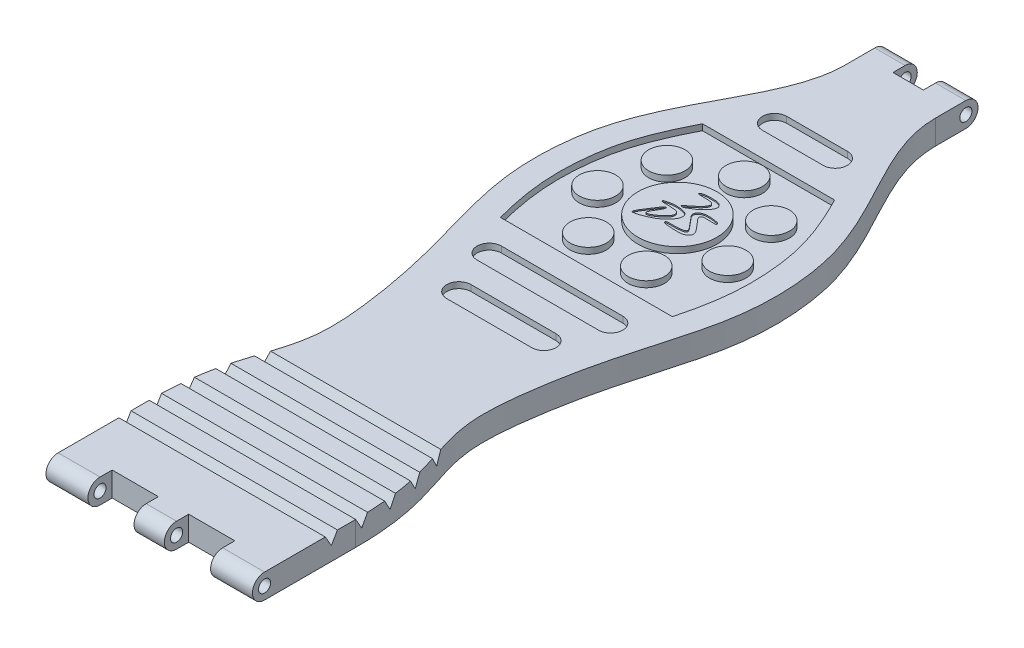
SolidWorks part; units mm, degrees
ref_plane "Front Plane" through (0, 0, 0) normal (0, 0, 1) x (1, 0, 0)
ref_plane "Top Plane" through (0, 0, 0) normal (0, 1, 0) x (1, 0, 0)
ref_plane "Right Plane" through (0, 0, 0) normal (1, 0, 0) x (0, 0, -1)
other "Configuration Table"
sketch "Sketch1" plane through (0, 0, 0) normal (0, 1, 0) x (1, 0, 0)
  line L0 (0, 0) -> (0, 152.4) construction
  line L2 (-21.59, 0) -> (21.59, 0)
  line L3 (-21.59, 0) -> (-21.59, 19.05)
  line L4 (-21.59, 19.05) -> (21.59, 19.05)
  line L5 (21.59, 0) -> (21.59, 19.05)
  line L6 (-21.59, 0) -> (21.59, 19.05) construction
  line L7 (-21.59, 19.05) -> (21.59, 0) construction
  line L8 (-9.525, 152.4) -> (9.525, 152.4)
  line L9 (-9.525, 152.4) -> (-9.525, 158.75)
  line L10 (-9.525, 158.75) -> (9.525, 158.75)
  line L11 (9.525, 152.4) -> (9.525, 158.75)
  line L12 (-9.525, 152.4) -> (9.525, 158.75) construction
  line L13 (-9.525, 158.75) -> (9.525, 152.4) construction
  spline S0 degree 3 poles (-9.525, 152.4) (-9.525, 140.7805) (-22.9495, 127.2801) (-26.9071, 91.7166) (-18.6052, 80.0483) (-14.4166, 41.5339) (-21.59, 36.242) (-21.59, 19.05) knots 0 0 0 0 0.318102 0.39652 0.741104 0.805759 1 1 1 1
  spline S1 degree 3 poles (9.525, 152.4) (9.525, 140.7805) (22.9495, 127.2801) (26.9071, 91.7166) (18.6052, 80.0483) (14.4166, 41.5339) (21.59, 36.242) (21.59, 19.05) knots 0 0 0 0 0.318102 0.39652 0.741104 0.805759 1 1 1 1
  point P7 (0, 9.525)
  point P12 (0, 155.575)
  dimension "D1" = 152.4
  dimension "D2" = 43.18
  dimension "D3" = 19.05
  dimension "D4" = 19.05
  dimension "D5" = 6.35
extrude "Boss-Extrude1" add sketch "Sketch1" against normal blind 5.08 contours S1 L8 S0 L4 | L2 L5 L4 L3 | L8 L11 L10 L9 region at (0, 0, -9.525) region at (0, 0, -84.0947) region at (0, 0, -155.575)
sketch "Sketch2" plane through (-21.59, 0, 0) normal (-1, 0, 0) x (0, 0, 1)
  line L0 (0, -5.08) -> (0, 0) construction
  circle A0 centre (0, -2.54) radius 2.54
extrude "Boss-Extrude2" add sketch "Sketch2" against normal up to surface (43.18 mm away) up to face at (21.59, -2.54, -9.525)
sketch "Sketch3" plane through (-9.525, 0, 0) normal (-1, 0, 0) x (0, 0, 1)
  line L0 (-158.75, -5.08) -> (-158.75, 0) construction
  circle A0 centre (-158.75, -2.54) radius 2.54
extrude "Boss-Extrude3" add sketch "Sketch3" against normal up to surface (19.05 mm away) up to face at (9.525, -2.54, -155.575)
sketch "Sketch4" plane through (-9.525, 0, 0) normal (-1, 0, 0) x (0, 0, 1)
  circle A0 centre (-158.75, -2.54) radius 1.27
  dimension "D1" = 2.54
extrude "Cut-Extrude1" cut sketch "Sketch4" against normal up to surface (19.05 mm away) up to face at (9.525, -2.54, -156.21)
sketch "Sketch5" plane through (-21.59, 0, 0) normal (-1, 0, 0) x (0, 0, 1)
  circle A0 centre (0, -2.54) radius 1.27
  dimension "D1" = 2.54
extrude "Cut-Extrude2" cut sketch "Sketch5" against normal up to surface (43.18 mm away) up to face at (21.59, -2.54, -8.89)
sketch "Sketch6" plane through (0, 0, 0) normal (0, 1, 0) x (1, 0, 0)
  line L0 (9.525, 161.29) -> (-9.525, 161.29) construction
  line L1 (-3.175, 2.54) -> (-12.827, 2.54)
  line L2 (-3.175, 2.54) -> (-3.175, -2.54)
  line L3 (-3.175, -2.54) -> (-12.827, -2.54)
  line L4 (-12.827, 2.54) -> (-12.827, -2.54)
  line L5 (-3.175, 2.54) -> (-12.827, -2.54) construction
  line L6 (-3.175, -2.54) -> (-12.827, 2.54) construction
  line L7 (-21.59, -2.54) -> (21.59, -2.54) construction
  line L8 (-3.175, 2.54) -> (3.175, 2.54) construction
  line L9 (3.175, 2.54) -> (12.827, 2.54)
  line L10 (3.175, 2.54) -> (3.175, -2.54)
  line L11 (3.175, -2.54) -> (12.827, -2.54)
  line L12 (12.827, 2.54) -> (12.827, -2.54)
  line L13 (3.175, 2.54) -> (12.827, -2.54) construction
  line L14 (3.175, -2.54) -> (12.827, 2.54) construction
  line L15 (3.175, 166.37) -> (-3.175, 166.37)
  line L16 (3.175, 166.37) -> (3.175, 156.21)
  line L17 (3.175, 156.21) -> (-3.175, 156.21)
  line L18 (-3.175, 166.37) -> (-3.175, 156.21)
  line L19 (3.175, 166.37) -> (-3.175, 156.21) construction
  line L20 (3.175, 156.21) -> (-3.175, 166.37) construction
  point P4 (-8.001, 0)
  point P5 (0, 2.54)
  point P6 (0, 161.29)
  point P13 (8.001, 0)
  dimension "D1" = 6.35
  dimension "D2" = 9.652
  dimension "D3" = 5.08
  dimension "D4" = 6.35
  dimension "D5" = 10.16
extrude "Cut-Extrude3" cut sketch "Sketch6" against normal up to surface (5.08 mm away) up to face at (0, -5.08, -99.2188)
sketch "Sketch7" plane through (0, 0, 0) normal (1, 0, 0) x (0, 0, -1)
  line L1 (15.24, 0) -> (13.97, -2.1997)
  line L2 (0, 0) -> (19.05, 0) construction
  line L3 (13.97, -2.1997) -> (12.7, 0)
  line L4 (12.7, 0) -> (15.24, 0)
  dimension "D1" = 2.54
  dimension "D2" = 12.7
extrude "Cut-Extrude4" cut sketch "Sketch7" against normal through all both and the other way through all
pattern_linear "LPattern1" count 5 spacing 6.35 along (0, 0, -1) of "Cut-Extrude4"
sketch "Sketch8" plane through (0, 0, 0) normal (0, 1, 0) x (1, 0, 0)
  line L0 (13.817, 127) -> (-13.817, 127)
  line L1 (17.983, 88.9) -> (-17.983, 88.9)
  line L2 (-12.7, 81.28) -> (12.7, 81.28) construction
  line L3 (-12.7, 83.82) -> (12.7, 83.82)
  line L4 (-12.7, 78.74) -> (12.7, 78.74)
  line L5 (-8.89, 71.12) -> (8.89, 71.12) construction
  line L6 (-8.89, 73.66) -> (8.89, 73.66)
  line L7 (-8.89, 68.58) -> (8.89, 68.58)
  line L8 (-6.35, 134.62) -> (6.35, 134.62) construction
  line L9 (-6.35, 137.16) -> (6.35, 137.16)
  line L10 (-6.35, 132.08) -> (6.35, 132.08)
  arc A0 (-12.7, 83.82) -> (-12.7, 78.74) centre (-12.7, 81.28) ccw
  arc A1 (12.7, 78.74) -> (12.7, 83.82) centre (12.7, 81.28) ccw
  arc A2 (-8.89, 73.66) -> (-8.89, 68.58) centre (-8.89, 71.12) ccw
  arc A3 (8.89, 68.58) -> (8.89, 73.66) centre (8.89, 71.12) ccw
  arc A4 (-6.35, 137.16) -> (-6.35, 132.08) centre (-6.35, 134.62) ccw
  arc A5 (6.35, 132.08) -> (6.35, 137.16) centre (6.35, 134.62) ccw
  spline S2 degree 3 poles (-2979.3893, -167.7654) (-176.8463, 335.583) (4.1325, 207.8677) (-4.9125, 147.4354) (-5.1756, 146.2435) (-6.1432, 142.7498) (-7.0227, 140.53) (-8.9915, 136.21) (-10.0828, 134.1078) (-12.2846, 129.9345) (-13.3956, 127.8637) (-15.4667, 123.7017) (-16.4265, 121.6114) (-17.6399, 118.4341) (-18.0068, 117.368) (-18.6494, 115.216) (-18.9221, 114.1359) (-19.61, 110.7817) (-19.8926, 108.4288) (-20.0513, 105.6351) (-20.0735, 105.0836) (-20.0997, 104.0031) (-20.1039, 103.4738) (-20.091, 101.9146) (-20.0489, 100.9131) (-19.8345, 97.9841) (-19.5747, 96.1313) (-18.8711, 92.4254) (-18.426, 90.5718) (-17.4006, 86.6995) (-16.82, 84.6813) (-15.5973, 80.3488) (-14.9558, 78.0349) (-13.7008, 72.9932) (-13.0877, 70.2658) (-12.255, 65.7755) (-11.9919, 64.2121) (-11.5046, 60.9368) (-11.2776, 59.2087) (-10.9298, 55.7161) (-10.8084, 53.9534) (-10.7771, 51.7959) (-10.7769, 51.3666) (-10.7906, 50.5129) (-10.8047, 50.0876) (-10.8691, 48.8383) (-10.9407, 48.0352) (-11.2283, 45.7083) (-11.5176, 44.2686) (-24.4626, -7.4426) (-102.0579, 68.6433) (2024.1668, -2162.2113) knots -1.484386 -1.484386 -1.484386 -1.484386 0.03125 0.03125 0.0625 0.0625 0.125 0.125 0.1875 0.1875 0.25 0.25 0.3125 0.3125 0.34375 0.34375 0.375 0.375 0.4375 0.4375 0.453125 0.453125 0.46875 0.46875 0.5 0.5 0.5625 0.5625 0.625 0.625 0.6875 0.6875 0.75 0.75 0.8125 0.8125 0.84375 0.84375 0.875 0.875 0.90625 0.90625 0.914063 0.914063 0.921875 0.921875 0.9375 0.9375 0.96875 0.96875 2.134953 2.134953 2.134953 2.134953 only from (-4.445, 152.4) to (-12.9652, 39.0961)
  spline S3 degree 3 poles (-13.817, 127) (-14.0242, 126.5945) (-14.2291, 126.1888) (-15.4667, 123.7017) (-16.4265, 121.6114) (-17.6399, 118.4341) (-18.0068, 117.368) (-18.6494, 115.216) (-18.9221, 114.1359) (-19.61, 110.7817) (-19.8926, 108.4288) (-20.0513, 105.6351) (-20.0735, 105.0836) (-20.0997, 104.0031) (-20.1039, 103.4738) (-20.091, 101.9146) (-20.0489, 100.9131) (-19.8345, 97.9841) (-19.5747, 96.1313) (-18.8871, 92.5099) (-18.4664, 90.7409) (-17.983, 88.9) knots 0.237804 0.237804 0.237804 0.237804 0.25 0.25 0.3125 0.3125 0.34375 0.34375 0.375 0.375 0.4375 0.4375 0.453125 0.453125 0.46875 0.46875 0.5 0.5 0.5625 0.5625 0.62215 0.62215 0.62215 0.62215
  spline S12 degree 3 poles (2979.3893, -167.7654) (176.8463, 335.583) (-4.1325, 207.8677) (4.9125, 147.4354) (5.1756, 146.2435) (6.1432, 142.7498) (7.0227, 140.53) (8.9915, 136.21) (10.0828, 134.1078) (12.2846, 129.9345) (13.3956, 127.8637) (15.4667, 123.7017) (16.4265, 121.6114) (17.6399, 118.4341) (18.0068, 117.368) (18.6494, 115.216) (18.9221, 114.1359) (19.61, 110.7817) (19.8926, 108.4288) (20.0513, 105.6351) (20.0735, 105.0836) (20.0997, 104.0031) (20.1039, 103.4738) (20.091, 101.9146) (20.0489, 100.9131) (19.8345, 97.9841) (19.5747, 96.1313) (18.8711, 92.4254) (18.426, 90.5718) (17.4006, 86.6995) (16.82, 84.6813) (15.5973, 80.3488) (14.9558, 78.0349) (13.7008, 72.9932) (13.0877, 70.2658) (12.255, 65.7755) (11.9919, 64.2121) (11.5046, 60.9368) (11.2776, 59.2087) (10.9298, 55.7161) (10.8084, 53.9534) (10.7771, 51.7959) (10.7769, 51.3666) (10.7906, 50.5129) (10.8047, 50.0876) (10.8691, 48.8383) (10.9407, 48.0352) (11.2283, 45.7083) (11.5176, 44.2686) (24.4626, -7.4426) (102.0579, 68.6433) (-2024.1668, -2162.2113) knots -1.484386 -1.484386 -1.484386 -1.484386 0.03125 0.03125 0.0625 0.0625 0.125 0.125 0.1875 0.1875 0.25 0.25 0.3125 0.3125 0.34375 0.34375 0.375 0.375 0.4375 0.4375 0.453125 0.453125 0.46875 0.46875 0.5 0.5 0.5625 0.5625 0.625 0.625 0.6875 0.6875 0.75 0.75 0.8125 0.8125 0.84375 0.84375 0.875 0.875 0.90625 0.90625 0.914063 0.914063 0.921875 0.921875 0.9375 0.9375 0.96875 0.96875 2.134953 2.134953 2.134953 2.134953 only from (4.445, 152.4) to (12.9652, 39.0961)
  spline S13 degree 3 poles (13.817, 127) (14.0242, 126.5945) (14.2291, 126.1888) (15.4667, 123.7017) (16.4265, 121.6114) (17.6399, 118.4341) (18.0068, 117.368) (18.6494, 115.216) (18.9221, 114.1359) (19.61, 110.7817) (19.8926, 108.4288) (20.0513, 105.6351) (20.0735, 105.0836) (20.0997, 104.0031) (20.1039, 103.4738) (20.091, 101.9146) (20.0489, 100.9131) (19.8345, 97.9841) (19.5747, 96.1313) (18.8871, 92.5099) (18.4664, 90.7409) (17.983, 88.9) knots 0.237804 0.237804 0.237804 0.237804 0.25 0.25 0.3125 0.3125 0.34375 0.34375 0.375 0.375 0.4375 0.4375 0.453125 0.453125 0.46875 0.46875 0.5 0.5 0.5625 0.5625 0.62215 0.62215 0.62215 0.62215
  point P10 (0, 81.28)
  point P17 (0, 71.12)
  point P24 (0, 134.62)
  dimension "D11" = 2.54
  dimension "D3" = 38.1
  dimension "D4" = 88.9
  dimension "D5" = 5.08
  dimension "D6" = 5.08
  dimension "D7" = 5.08
  dimension "D8" = 12.7
  dimension "D9" = 25.4
  dimension "D10" = 17.78
  dimension "D1" = 5.08
  dimension "D2" = 5.08
extrude "Cut-Extrude5" cut sketch "Sketch8" against normal blind 1.27
sketch "Sketch10" plane through (0, -1.27, 0) normal (0, 1, 0) x (1, 0, 0)
  line L0 (0, 127) -> (0, 107.95) construction
  line L1 (13.817, 127) -> (-13.817, 127) construction
  line L2 (0, 107.95) -> (0, 88.9) construction
  line L3 (-17.983, 88.9) -> (17.983, 88.9) construction
  circle A0 centre (0, 107.95) radius 13.97 construction
  circle A1 centre (0, 121.92) radius 3.81
  dimension "D1" = 27.94
  dimension "D2" = 7.62
extrude "Boss-Extrude4" add sketch "Sketch10" along normal up to surface (1.27 mm away) up to face at (0, 0, -134.62)
ref_axis "Axis1" through (0, -1.27, -107.95) along (0, 1, 0)
pattern_circular "CirPattern1" count 7 over 360 about axis through (0, -1.27, -107.95) along (0, 1, 0) of "Boss-Extrude4"
sketch "Sketch11" plane through (0, -1.27, 0) normal (0, 1, 0) x (1, 0, 0)
  circle A0 centre (0, 107.95) radius 8.255
  dimension "D1" = 16.51
extrude "Boss-Extrude5" add sketch "Sketch11" along normal up to surface (1.27 mm away) up to face at (0, 0, -134.62)
sketch "Sketch13" plane through (0, 0, 0) normal (0, 1, 0) x (1, 0, 0)
  line L0 (2.189, 110.8352) -> (135.5223, 110.8352) construction
  line L1 (-4.7639, 104.9913) -> (-2.9762, 107.7207)
  spline S0 degree 3 poles (-1.5118, 114.0219) (-1.4421, 114.1685) (-0.9455, 114.3858) (-0.0135, 114.4891) (1.0558, 114.4891) (2.0477, 114.3932) (2.7056, 114.0722) (3.0994, 113.3783) (2.7383, 112.4905) (2.047, 111.6691) (1.2567, 110.933) (0.4306, 110.4557) (-0.2135, 110.0539) (-0.7571, 109.8009) (-1.0928, 109.8229) (-1.1827, 109.8991) knots 0 0 0 0 0.042326 0.13724 0.264506 0.335188 0.412965 0.455949 0.542825 0.649198 0.759646 0.837282 0.91245 0.970561 1 1 1 1
  spline S1 degree 3 poles (-1.5118, 114.0219) (-1.5295, 113.9845) (-1.5573, 113.824) (-1.0288, 113.8407) (-0.5399, 113.7816) (0.2213, 113.8271) (0.9351, 113.7381) (1.5336, 113.632) (1.8798, 113.1647) (1.5642, 112.4988) (1.1006, 111.9536) (0.4533, 111.3495) (-0.1661, 110.8633) (-0.7411, 110.385) (-1.0916, 110.1712) (-1.2246, 109.9764) (-1.218, 109.9291) (-1.1827, 109.8991) knots 0 0 0 0 0.011373 0.060874 0.126759 0.224901 0.323556 0.397977 0.434798 0.518924 0.62848 0.708164 0.839679 0.91754 0.981655 0.988925 1 1 1 1
  spline S2 degree 3 poles (-4.0381, 108.868) (-4.0409, 108.9843) (-3.36, 109.1903) (-2.6615, 109.343) (-1.4635, 109.4627) (-0.3391, 109.2894) (0.8414, 108.9393) (1.0473, 107.8102) (0.6248, 106.9607) (-0.101, 106.2489) (-0.9279, 105.3305) (-2.1379, 104.6142) (-3.3518, 104.1226) (-4.2895, 103.7796) (-4.8649, 103.6934) (-5.2364, 103.6241) (-5.3578, 103.8805) (-5.0814, 104.3794) (-5.1023, 104.4747) (-4.7639, 104.9913) knots 0 0 0 0 0.035651 0.092587 0.171081 0.257807 0.326935 0.389171 0.454193 0.508585 0.589509 0.697497 0.781321 0.850811 0.889001 0.904316 0.914583 0.937149 1 1 1 1
  spline S3 degree 3 poles (-2.9762, 107.7207) (-2.9089, 107.8271) (-2.7822, 107.9483) (-2.6036, 108.0702) (-2.4627, 108.0991) (-2.3116, 107.9763) (-2.3905, 107.6566) (-2.6246, 107.1553) (-3.0601, 106.4363) (-3.4749, 105.7713) (-3.6685, 105.3061) (-3.7083, 104.88) (-3.0246, 105.0224) (-2.5317, 105.3264) (-1.8156, 105.7718) (-1.2111, 106.3304) (-0.6929, 106.858) (-0.3311, 107.3259) (-0.2918, 107.7881) (-0.4264, 108.4649) (-1.4839, 108.5803) (-2.4157, 108.6591) (-3.2071, 108.6662) (-3.6799, 108.6418) (-3.9644, 108.6667) (-4.0362, 108.7898) (-4.0381, 108.868) knots 0 0 0 0 0.028901 0.040122 0.05025 0.059683 0.079637 0.116476 0.193844 0.272447 0.293654 0.317292 0.348338 0.411714 0.470913 0.537541 0.602808 0.644437 0.668799 0.709518 0.788261 0.872675 0.94124 0.966275 0.986327 1 1 1 1
  spline S4 degree 3 poles (5.9171, 110.2609) (5.8974, 110.415) (5.7774, 110.6467) (5.1885, 110.7293) (4.5024, 110.8824) (3.5978, 110.9037) (2.7444, 110.8738) (2.0162, 110.5477) (1.6091, 110.0923) (1.4487, 109.4119) (2.0995, 108.6454) (2.7732, 107.7583) (3.4813, 107.0268) (3.866, 106.4857) (4.0233, 106.1213) (3.8689, 105.8808) (3.5188, 105.7019) (2.8314, 105.6248) (1.8945, 105.5322) (1.0181, 105.557) (0.4054, 105.5553) (0.1075, 105.478) (-0.0748, 105.2311) (0.4169, 104.9671) (0.9806, 104.9339) (1.8717, 104.8398) (2.871, 104.8642) (3.8472, 104.7899) (4.6144, 105.0934) (5.0467, 105.4347) (5.2361, 105.7908) (5.2894, 106.1821) (5.0968, 106.6365) (4.8026, 107.0862) (4.4548, 107.4389) (4.2094, 107.7821) (3.9322, 108.1043) (3.5674, 108.4976) (3.2306, 108.9226) (2.9071, 109.3099) (2.7015, 109.6882) (2.9328, 110.0781) (3.4295, 110.2127) (4.1664, 110.1262) (4.9447, 110.1813) (5.5436, 110.1349) (5.8115, 110.1708) (5.9171, 110.2609) (5.8974, 110.415) (5.7774, 110.6467) knots -0.013676 -0.007513 -0.004089 0 0.007968 0.022841 0.058736 0.08767 0.120199 0.151122 0.171586 0.184517 0.223593 0.26853 0.310885 0.3315 0.343293 0.34938 0.360543 0.384926 0.423995 0.46313 0.480211 0.490538 0.495988 0.50844 0.53378 0.56595 0.602255 0.644043 0.670076 0.690282 0.702523 0.713089 0.732151 0.754234 0.771685 0.785767 0.800094 0.817888 0.844235 0.858518 0.874128 0.886178 0.901952 0.927093 0.966949 0.986324 0.992487 0.995911 1 1.007968 1.022841 1.058736 only from (5.8979, 110.3745) to (5.8979, 110.3745)
extrude "Cut-Extrude6" cut sketch "Sketch13" against normal blind 0.254
scale "Scale1" scale about centroid uniform scaling yes scale factor 1.5
